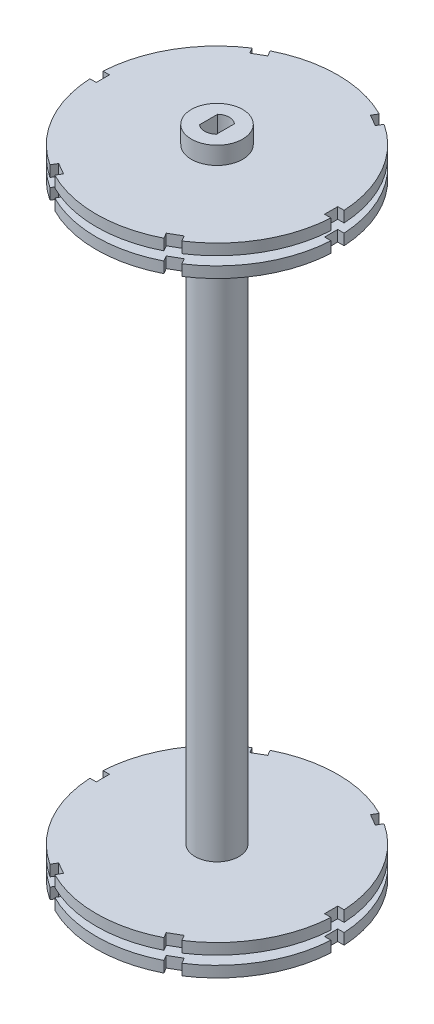
SolidWorks part; units mm, degrees
note: '?' marks a value the reader was unsure of.
ref_plane "Front Plane" through (0, 0, 0) normal (0, 0, 1) x (1, 0, 0)
ref_plane "Top Plane" through (0, 0, 0) normal (0, 1, 0) x (1, 0, 0)
ref_plane "Right Plane" through (0, 0, 0) normal (1, 0, 0) x (0, 0, -1)
sketch "Sketch1" plane through (0, 0, 0) normal (0, 1, 0) x (1, 0, 0)
  line L0 (1.9, 2.0567) -> (1.9, -2.0567)
  line L1 (-1.9, -2.0567) -> (-1.9, 2.0567)
  line L2 (-1.9, 2.0567) -> (-1.9, 5.5329)
  line L3 (1.9, 2.0567) -> (1.9, 5.5329)
  line L4 (-1.9, -2.0567) -> (-1.9, -5.5329)
  line L5 (1.9, -2.0567) -> (1.9, -5.5329)
  circle A0 centre (0, 0) radius 2.8
  circle A1 centre (0, 0) radius 5.85
  dimension "D1" = 5.6
  dimension "D4" = 11.7
  dimension "D2" = 1.9
  dimension "D3" = 1.9
extrude "Boss-Extrude1" add sketch "Sketch1" along normal blind 6.5 contours L2 A1 L4 A0 | L3 A1 L2 A0 | L5 A1 L3 A0 | L4 A1 L5 A0 | L1 A0 | L0 A0
sketch "Sketch2" plane through (0, 6.5, 0) normal (0, 1, 0) x (1, 0, 0)
  circle A0 centre (0, 0) radius 27.5
  dimension "D1" = 55
extrude "Boss-Extrude2" add sketch "Sketch2" against normal blind 2.5
sketch "Sketch3" plane through (0, 4, 0) normal (0, -1, 0) x (1, 0, 0)
  line L2 (-1.9, 2.0567) -> (-1.9, -2.0567)
  line L3 (1.9, -2.0567) -> (1.9, 2.0567)
  line L4 (-1.9, 2.0567) -> (-1.9, -2.0567)
  line L5 (1.9, -2.0567) -> (1.9, 2.0567)
  arc A2 (1.9, 2.0567) -> (-1.9, 2.0567) centre (0, 0) ccw
  arc A3 (-1.9, -2.0567) -> (1.9, -2.0567) centre (0, 0) ccw
  arc A4 (1.9, 2.0567) -> (-1.9, 2.0567) centre (0, 0) ccw
  arc A5 (-1.9, -2.0567) -> (1.9, -2.0567) centre (0, 0) ccw
  dimension "D1" = 0
extrude "Cut-Extrude1" cut sketch "Sketch3" against normal blind 8
sketch "Sketch4" plane through (0, 6.5, 0) normal (0, 1, 0) x (1, 0, 0)
  line L5 (-53.8948, 0) -> (53.8948, 0) construction
  line L6 (0, 31.6457) -> (0, -31.6457) construction
  line L7 (14.299, -21.7667) -> (15.799, -24.3647)
  line L9 (26, 1.5) -> (29, 1.5)
  line L10 (26, 1.5) -> (26, -1.5)
  line L11 (26, -1.5) -> (29, -1.5)
  line L12 (29, 1.5) -> (29, -1.5)
  line L13 (26, 1.5) -> (29, -1.5) construction
  line L14 (26, -1.5) -> (29, 1.5) construction
  line L29 (14.299, -21.7667) -> (11.701, -23.2667)
  line L30 (11.701, -23.2667) -> (13.201, -25.8647)
  line L35 (15.799, -24.3647) -> (13.201, -25.8647)
  line L36 (14.299, -21.7667) -> (13.201, -25.8647) construction
  line L41 (11.701, -23.2667) -> (15.799, -24.3647) construction
  line L42 (-26.9474, 46.6742) -> (26.9474, -46.6742) construction
  line L43 (-11.701, -23.2667) -> (-13.201, -25.8647)
  line L44 (-11.701, -23.2667) -> (-14.299, -21.7667)
  line L45 (-14.299, -21.7667) -> (-15.799, -24.3647)
  line L46 (-13.201, -25.8647) -> (-15.799, -24.3647)
  line L47 (-11.701, -23.2667) -> (-15.799, -24.3647) construction
  line L48 (-14.299, -21.7667) -> (-13.201, -25.8647) construction
  line L49 (26.9474, 46.6742) -> (-26.9474, -46.6742) construction
  line L50 (-26, -1.5) -> (-29, -1.5)
  line L51 (-26, -1.5) -> (-26, 1.5)
  line L52 (-26, 1.5) -> (-29, 1.5)
  line L53 (-29, -1.5) -> (-29, 1.5)
  line L54 (-26, -1.5) -> (-29, 1.5) construction
  line L55 (-26, 1.5) -> (-29, -1.5) construction
  line L56 (53.8948, 0) -> (-53.8948, 0) construction
  line L57 (-14.299, 21.7667) -> (-15.799, 24.3647)
  line L58 (-14.299, 21.7667) -> (-11.701, 23.2667)
  line L59 (-11.701, 23.2667) -> (-13.201, 25.8647)
  line L60 (-15.799, 24.3647) -> (-13.201, 25.8647)
  line L61 (-14.299, 21.7667) -> (-13.201, 25.8647) construction
  line L62 (-11.701, 23.2667) -> (-15.799, 24.3647) construction
  line L63 (26.9474, -46.6742) -> (-26.9474, 46.6742) construction
  line L64 (11.701, 23.2667) -> (13.201, 25.8647)
  line L65 (11.701, 23.2667) -> (14.299, 21.7667)
  line L66 (14.299, 21.7667) -> (15.799, 24.3647)
  line L67 (13.201, 25.8647) -> (15.799, 24.3647)
  line L68 (11.701, 23.2667) -> (15.799, 24.3647) construction
  line L69 (14.299, 21.7667) -> (13.201, 25.8647) construction
  line L70 (-26.9474, -46.6742) -> (26.9474, 46.6742) construction
  circle A0 centre (0, 0) radius 27.5 construction
  point P3 (0, 0)
  point P8 (0, 0)
  point P12 (27.5, 0)
  point P19 (13.75, -23.8157)
  point P26 (-13.75, -23.8157)
  point P33 (-27.5, 0)
  point P40 (-13.75, 23.8157)
  point P47 (13.75, 23.8157)
  dimension "D4" = 3
  dimension "D5" = 3
ref_axis "Axis1" through (0, 6.5, 0) along (0, -1, 0)?
extrude "Cut-Extrude2" cut sketch "Sketch4" against normal blind 10
sketch "Sketch5" plane through (0, 6.5, 0) normal (0, 1, 0) x (1, 0, 0)
  circle A0 centre (0, 0) radius 5
  dimension "D1" = 10
extrude "Boss-Extrude3" add sketch "Sketch5" along normal blind 140
ref_plane "Plane1" through (0, 76.5, 0) normal (0, 1, 0) x (1, 0, 0)
mirror "Mirror1" about plane through (0, 76.5, 0) normal (0, 1, 0) of "Boss-Extrude2"
mirror "Mirror2" about plane through (0, 76.5, 0) normal (0, 1, 0) of "Boss-Extrude1"
ref_plane "Plane2" through (0, 7.5, 0) normal (0, 1, 0) x (1, 0, 0)
mirror "Mirror3" about plane through (0, 7.5, 0) normal (0, 1, 0) of "Cut-Extrude2", "Boss-Extrude2", "Cut-Extrude1"
sketch "Sketch6" plane through (0, 11, 0) normal (0, -1, 0) x (1, 0, 0)
  line L2 (-1.9, 2.0567) -> (-1.9, -2.0567)
  line L3 (1.9, -2.0567) -> (1.9, 2.0567)
  line L4 (-1.9, 2.0567) -> (-1.9, -2.0567)
  line L5 (1.9, -2.0567) -> (1.9, 2.0567)
  arc A2 (1.9, 2.0567) -> (-1.9, 2.0567) centre (0, 0) ccw
  arc A3 (-1.9, -2.0567) -> (1.9, -2.0567) centre (0, 0) ccw
  arc A4 (1.9, 2.0567) -> (-1.9, 2.0567) centre (0, 0) ccw
  arc A5 (-1.9, -2.0567) -> (1.9, -2.0567) centre (0, 0) ccw
  dimension "D1" = 0
extrude "Cut-Extrude3" cut sketch "Sketch6" against normal blind 15
ref_plane "Plane3" through (0, 145.5, 0) normal (0, -1, 0) x (-1, 0, 0)
mirror "Mirror5" about plane through (0, 76.5, 0) normal (0, 1, 0) of "Cut-Extrude2"
mirror "Mirror6" about plane through (0, 145.5, 0) normal (0, -1, 0) of "Mirror5", "Mirror1"
sketch "Sketch7" plane through (0, 153, 0) normal (0, 1, 0) x (1, 0, 0)
